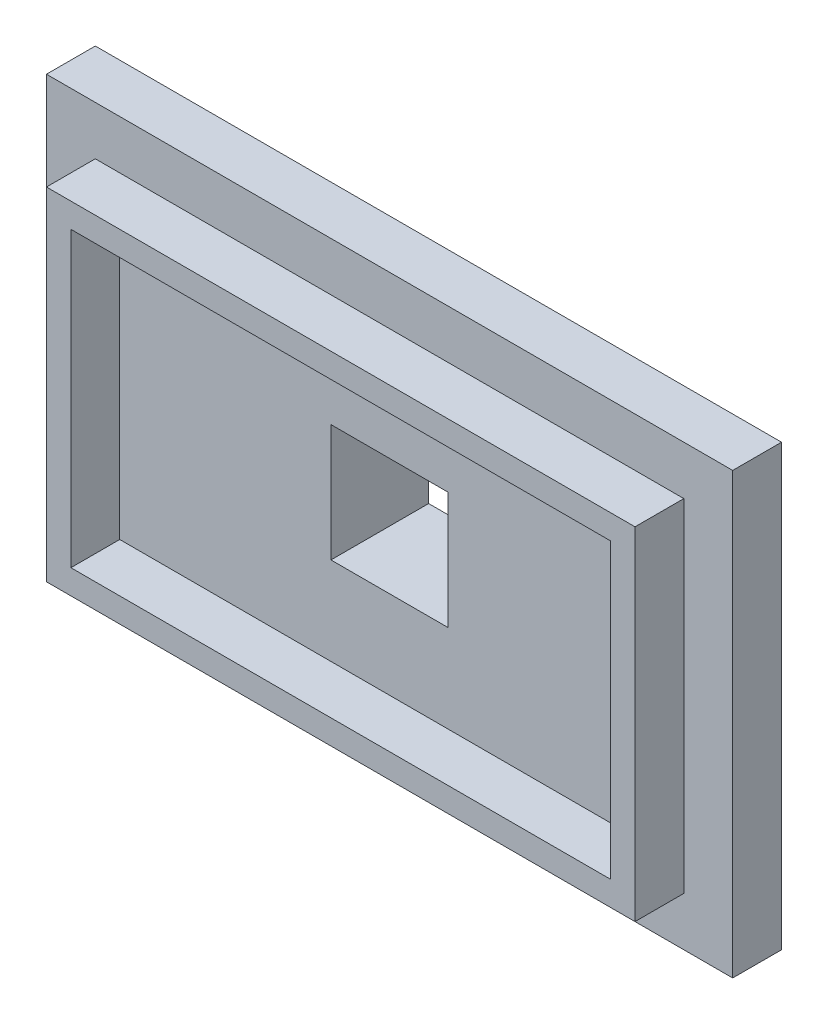
SolidWorks part; units mm, degrees
material "Polyurethane Foam Rigid"
ref_plane "X-Y Datum" through (0, 0, 0) normal (0, 0, 1) x (1, 0, 0)
ref_plane "X-Z Datum" through (0, 0, 0) normal (0, 1, 0) x (1, 0, 0)
ref_plane "Y-Z Datum" through (0, 0, 0) normal (1, 0, 0) x (0, 0, -1)
sketch "Sketch1" plane through (0, 0, 0) normal (0, 0, 1) x (1, 0, 0)
  line L0 (-153.0248, -88.9) -> (-153.0248, 88.9)
  line L1 (-178.4248, -114.3) -> (178.4248, -114.3)
  line L2 (-178.4248, -114.3) -> (-178.4248, 114.3)
  line L3 (-178.4248, 114.3) -> (178.4248, 114.3)
  line L4 (178.4248, -114.3) -> (178.4248, 114.3)
  line L5 (-178.4248, -114.3) -> (178.4248, 114.3) construction
  line L6 (-178.4248, 114.3) -> (178.4248, -114.3) construction
  line L7 (-153.0248, 88.9) -> (153.0248, 88.9)
  line L8 (153.0248, -88.9) -> (153.0248, 88.9)
  line L9 (-153.0248, -88.9) -> (153.0248, -88.9)
  point P0 (0, 0)
  dimension "D1" = 356.8497
  dimension "D2" = 228.6
  dimension "D3" = 25.4
extrude "Boss-Extrude1" add sketch "Sketch1" along normal blind 25.4
extrude "Boss-Extrude2" add sketch "Sketch1<3>" along normal blind 25.4 and the other way blind 25.4 contours L0 L9 L8 L7 region at (0, 0, 0)
sketch "Sketch1<3>" plane through (0, 0, 0) normal (0, 0, 1) x (1, 0, 0) same geometry as "Sketch1"
sketch "Sketch2" plane through (0, 0, -25.4) normal (0, 0, -1) x (-1, 0, 0)
  line L0 (-153.0248, -88.9) -> (-153.0248, 88.9) construction
  line L2 (0, -88.9) -> (0, 88.9) construction
  line L3 (-153.0248, 88.9) -> (153.0248, 88.9) construction
  line L10 (153.0248, 88.9) -> (-153.0248, 88.9) construction
  line L19 (-30.48, -30.48) -> (30.48, -30.48)
  line L20 (-30.48, -30.48) -> (-30.48, 30.48)
  line L21 (-30.48, 30.48) -> (30.48, 30.48)
  line L22 (30.48, -30.48) -> (30.48, 30.48)
  line L23 (-30.48, -30.48) -> (30.48, 30.48) construction
  line L24 (-30.48, 30.48) -> (30.48, -30.48) construction
  point P6 (0, 0)
  point P12 (0, 0)
  dimension "D1" = 60.96
  dimension "D2" = 60.96
  dimension "D3" = 122.5448
  dimension "D4" = 58.42
extrude "Cut-Extrude1" cut sketch "Sketch2" against normal through all
sketch "Sketch3" plane through (0, 0, 25.4) normal (0, 0, 1) x (1, 0, 0)
  line L0 (-140.3248, -76.2) -> (-140.3248, 76.2)
  line L1 (-153.0248, -88.9) -> (153.0248, -88.9)
  line L2 (-153.0248, -88.9) -> (-153.0248, 88.9)
  line L3 (-153.0248, 88.9) -> (153.0248, 88.9)
  line L4 (153.0248, -88.9) -> (153.0248, 88.9)
  line L5 (-153.0248, -88.9) -> (153.0248, 88.9) construction
  line L6 (-153.0248, 88.9) -> (153.0248, -88.9) construction
  line L7 (-140.3248, 76.2) -> (140.3248, 76.2)
  line L8 (140.3248, -76.2) -> (140.3248, 76.2)
  line L9 (-140.3248, -76.2) -> (140.3248, -76.2)
  point P0 (0, 0)
  dimension "D1" = 177.8
  dimension "D2" = 306.0497
  dimension "D3" = 12.7
extrude "Boss-Extrude3" add sketch "Sketch3" along normal blind 25.4
